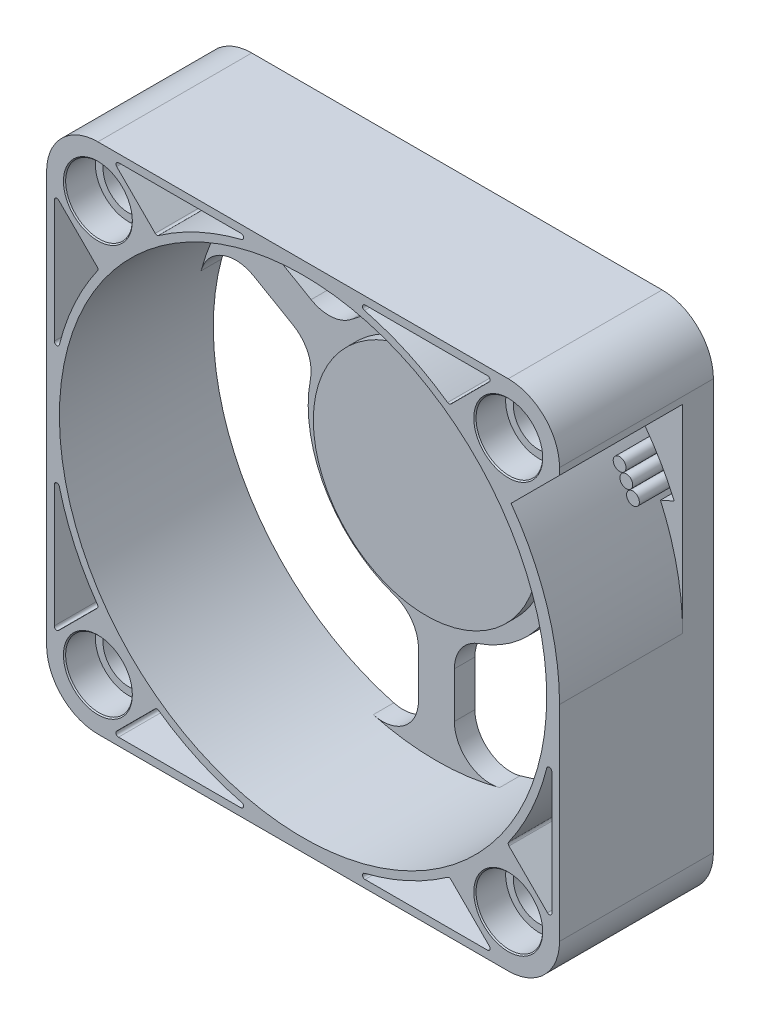
SolidWorks part; units mm, degrees
material "ABS"
ref_plane "Спереди" through (0, 0, 0) normal (0, 0, 1) x (1, 0, 0)
ref_plane "Сверху" through (0, 0, 0) normal (0, 1, 0) x (1, 0, 0)
ref_plane "Справа" through (0, 0, 0) normal (1, 0, 0) x (0, 0, -1)
sketch "Эскиз1" plane through (0, 0, 0) normal (0, 0, 1) x (1, 0, 0)
  line L0 (0, 25) -> (0, -25) construction
  line L1 (-20, -25) -> (20, -25)
  line L2 (-25, -20) -> (-25, 20)
  line L3 (-20, 25) -> (20, 25)
  line L4 (25, -20) -> (25, 20)
  line L5 (1.75, -12.3769) -> (1.75, -23.6854)
  line L6 (-1.75, -12.3769) -> (-1.75, -23.6854)
  line L7 (0, 0) -> (20.5681, 11.875) construction
  line L8 (0, 0) -> (-20.5681, 11.875) construction
  line L9 (-19.6372, 13.3583) -> (-9.8437, 7.704)
  line L10 (-21.3872, 10.3272) -> (-11.5937, 4.6729)
  line L11 (-11.5937, 4.6729) -> (-9.8437, 7.704) construction
  line L12 (-1.75, -12.3769) -> (1.75, -12.3769) construction
  line L13 (8.6423, 9.0311) -> (18.5935, 14.7764)
  line L14 (22.0935, 8.7143) -> (12.1423, 2.9689)
  line L15 (12.1423, 2.9689) -> (8.6423, 9.0311) construction
  arc A0 (-20, -25) -> (-25, -20) centre (-20, -20) cw
  arc A1 (20, -25) -> (25, -20) centre (20, -20) ccw
  arc A2 (20, 25) -> (25, 20) centre (20, 20) cw
  arc A3 (-25, 20) -> (-20, 25) centre (-20, 20) cw
  circle A4 centre (0, 0) radius 12.5
  circle A5 centre (0, 0) radius 23.75
  arc A6 (-16.7861, 16.8014) -> (-16.0624, 11.2943) centre (-14.3124, 14.3254) ccw
  arc A7 (-22.9435, 6.1365) -> (-17.8124, 8.2633) centre (-19.5624, 5.2322) cw
  arc A8 (-12.2142, 9.0726) -> (-8.1752, 9.456) centre (-10.4642, 12.1037) ccw
  arc A9 (-13.9642, 6.0415) -> (-12.2767, 2.3519) centre (-15.7142, 3.0104) cw
  arc A10 (-4.1016, -11.8079) -> (-1.75, -15.1141) centre (-5.25, -15.1141) cw
  arc A11 (1.75, -15.1141) -> (4.1016, -11.8079) centre (5.25, -15.1141) cw
  arc A12 (1.75, -19.5576) -> (6.1574, -22.9379) centre (5.25, -19.5576) ccw
  arc A13 (-1.75, -19.5576) -> (-6.1574, -22.9379) centre (-5.25, -19.5576) cw
  arc A14 (6.9999, 10.3562) -> (10.7099, 10.2248) centre (8.9599, 13.2559) ccw
  arc A15 (12.4687, 0.884) -> (14.2099, 4.1627) centre (15.9599, 1.1316) cw
  arc A16 (18.2059, 6.4697) -> (23.4051, 4.033) centre (19.9559, 3.4386) cw
  arc A17 (14.7059, 12.5319) -> (15.1952, 18.2529) centre (12.9559, 15.563) ccw
  dimension "D1" = 5
  dimension "D3" = 25
  dimension "D4" = 47.5
  dimension "D7" = 3.5
  dimension "D2" = 50
  dimension "D5" = 60
  dimension "D6" = 3.5
  dimension "D8" = 7
extrude "Бобышка-Вытянуть1" add sketch "Эскиз1" along normal blind 15 contours A3 L2 A0 L1 A1 L4 A2 L3 A5 | A6 A5 L9 | A5 A7 L10 | L9 A5 L10 A4 | A17 L13 A5 | A14 A4 L13 | A8 L9 A4 | L10 A9 A4 | A4 | L14 A16 A5 | A4 A15 L14 | L14 A5 L13 A4 | L6 A5 L5 A4 | L5 A11 A4 | A4 A10 L6 | L6 A13 A5 | A12 L5 A5 region at (-23.0355, -23.0355, 0) region at (2.2662, -12.8886, 0) region at (0, -18.0937, 0) region at (0, 0, 0) region at (-2.2662, -12.8886, 0) region at (2.7644, -22.6383, 0) region at (-2.7644, -22.6383, 0) region at (-12.295, 4.4817, 0) region at (12.6849, 2.7888, 0) region at (-15.6696, 9.0469, 0) region at (15.5872, 8.9993, 0) region at (21.5701, 7.1376, 0) region at (-20.9876, 8.9251, 0) region at (-10.0287, 8.4069, 0) region at (8.7576, 9.5911, 0) region at (16.9664, 15.1115, 0) region at (-18.2231, 13.7132, 0)
sketch "Эскиз2" plane through (0, 0, 15) normal (0, 0, 1) x (1, 0, 0)
  circle A0 centre (0, 0) radius 23.75
  arc A1 (15.1952, 18.2529) -> (-16.7861, 16.8014) centre (0, 0) ccw construction
extrude "Вырез-Вытянуть1" cut sketch "Эскиз2" against normal blind 13
sketch "Эскиз3" plane through (0, 0, 15) normal (0, 0, 1) x (1, 0, 0)
  line L0 (0, 20) -> (0, -20) construction
  line L1 (-20, -20) -> (20, -20) construction
  line L2 (-20, -20) -> (-20, 20) construction
  line L3 (-20, 20) -> (20, 20) construction
  line L4 (20, -20) -> (20, 20) construction
  dimension "D1" = 40
hole_wizard "Цековка для  болта с шестигранной головкой M51" positions "Эскиз4" profile "Эскиз5" counterbore size "M5" standard "ISO" end condition up to next
sketch "Эскиз4" plane through (0, 0, 15) normal (0, 0, 1) x (1, 0, 0)
  point P0 (-20, 20)
  point P3 (20, 20)
  point P6 (20, -20)
  point P9 (-20, -20)
sketch "Эскиз5" plane through (-20, 20, 15) normal (1, 0, 0) x (0, -1, 0)
  line L0 (0, 0) -> (0, 15)
  line L1 (0, 15) -> (2.5, 15)
  line L3 (2.5, 15) -> (2.5, 3)
  line L4 (3.25, 3) -> (2.5, 3)
  line L5 (3.25, 3) -> (3.25, 0.11)
  line L6 (3.25, 0.11) -> (3.36, 0)
  line L7 (3.36, 0) -> (0, 0)
  line L8 (-3.25, 0.11) -> (-3.36, 0) construction
  line L11 (0, -6.35) -> (0, 107.95) construction
  dimension "Диаметр сквозного отверстия" = 5
  dimension "Глубина сквозного отверстия" = 15
  dimension "Диаметр цековки" = 6.5
  dimension "Глубина цековки" = 3
  dimension "Диаметр передней зенковки" = 6.72
  dimension "Угол передней зенковки" = 90
sketch "Эскиз6" plane through (0, 0, 15) normal (0, 0, 1) x (1, 0, 0)
  line L0 (0, 0) -> (20, 20) construction
  line L1 (6.0467, 24.25) -> (17.9896, 24.25)
  line L2 (-20, 25) -> (20, 25) construction
  line L3 (14.4125, 20.0694) -> (18.1664, 23.8232)
  line L4 (24.25, -6.0467) -> (24.25, -17.9896)
  line L5 (25, -20) -> (25, 20) construction
  line L6 (20.0694, 14.4125) -> (23.8232, 18.1664)
  line L7 (24.25, 17.9896) -> (24.25, 6.0467)
  line L8 (20.0694, -14.4125) -> (23.8232, -18.1664)
  line L9 (14.4125, -20.0694) -> (18.1664, -23.8232)
  line L10 (17.9896, -24.25) -> (6.0467, -24.25)
  line L11 (-6.0467, -24.25) -> (-17.9896, -24.25)
  line L12 (-14.4125, -20.0694) -> (-18.1664, -23.8232)
  line L13 (-20.0694, -14.4125) -> (-23.8232, -18.1664)
  line L14 (-24.25, -17.9896) -> (-24.25, -6.0467)
  line L15 (-24.25, 6.0467) -> (-24.25, 17.9896)
  line L16 (-20.0694, 14.4125) -> (-23.8232, 18.1664)
  line L17 (-14.4125, 20.0694) -> (-18.1664, 23.8232)
  line L18 (-17.9896, 24.25) -> (-6.0467, 24.25)
  arc A0 (23.7576, 5.9856) -> (20.0416, 14.0919) centre (0, 0) ccw
  arc A1 (6.0467, 24.25) -> (5.9856, 23.7576) centre (6.0467, 24) ccw
  arc A2 (18.1664, 23.8232) -> (17.9896, 24.25) centre (17.9896, 24) ccw
  arc A3 (14.0919, 20.0416) -> (14.4125, 20.0694) centre (14.2357, 20.2461) ccw
  arc A4 (23.8232, 18.1664) -> (24.25, 17.9896) centre (24, 17.9896) cw
  arc A5 (24.25, 6.0467) -> (23.7576, 5.9856) centre (24, 6.0467) cw
  arc A6 (20.0694, 14.4125) -> (20.0416, 14.0919) centre (20.2461, 14.2357) ccw
  arc A7 (14.0919, 20.0416) -> (5.9856, 23.7576) centre (0, 0) ccw
  arc A8 (24.25, -6.0467) -> (23.7576, -5.9856) centre (24, -6.0467) ccw
  arc A9 (23.8232, -18.1664) -> (24.25, -17.9896) centre (24, -17.9896) ccw
  arc A10 (20.0416, -14.0919) -> (20.0694, -14.4125) centre (20.2461, -14.2357) ccw
  arc A11 (20.0416, -14.0919) -> (23.7576, -5.9856) centre (0, 0) ccw
  arc A12 (18.1664, -23.8232) -> (17.9896, -24.25) centre (17.9896, -24) cw
  arc A13 (6.0467, -24.25) -> (5.9856, -23.7576) centre (6.0467, -24) cw
  arc A14 (5.9856, -23.7576) -> (14.0919, -20.0416) centre (0, 0) ccw
  arc A15 (14.4125, -20.0694) -> (14.0919, -20.0416) centre (14.2357, -20.2461) ccw
  arc A16 (-6.0467, -24.25) -> (-5.9856, -23.7576) centre (-6.0467, -24) ccw
  arc A17 (-18.1664, -23.8232) -> (-17.9896, -24.25) centre (-17.9896, -24) ccw
  arc A18 (-14.0919, -20.0416) -> (-14.4125, -20.0694) centre (-14.2357, -20.2461) ccw
  arc A19 (-14.0919, -20.0416) -> (-5.9856, -23.7576) centre (0, 0) ccw
  arc A20 (-23.8232, -18.1664) -> (-24.25, -17.9896) centre (-24, -17.9896) cw
  arc A21 (-24.25, -6.0467) -> (-23.7576, -5.9856) centre (-24, -6.0467) cw
  arc A22 (-23.7576, -5.9856) -> (-20.0416, -14.0919) centre (0, 0) ccw
  arc A23 (-20.0694, -14.4125) -> (-20.0416, -14.0919) centre (-20.2461, -14.2357) ccw
  arc A24 (-24.25, 6.0467) -> (-23.7576, 5.9856) centre (-24, 6.0467) ccw
  arc A25 (-23.8232, 18.1664) -> (-24.25, 17.9896) centre (-24, 17.9896) ccw
  arc A26 (-20.0416, 14.0919) -> (-20.0694, 14.4125) centre (-20.2461, 14.2357) ccw
  arc A27 (-20.0416, 14.0919) -> (-23.7576, 5.9856) centre (0, 0) ccw
  arc A28 (-18.1664, 23.8232) -> (-17.9896, 24.25) centre (-17.9896, 24) cw
  arc A29 (-6.0467, 24.25) -> (-5.9856, 23.7576) centre (-6.0467, 24) cw
  arc A30 (-5.9856, 23.7576) -> (-14.0919, 20.0416) centre (0, 0) ccw
  arc A31 (-14.4125, 20.0694) -> (-14.0919, 20.0416) centre (-14.2357, 20.2461) ccw
  point P86 (0, 0)
  dimension "D1" = 49
  dimension "D4" = 0.25
  dimension "D2" = 0.75
  dimension "D3" = 4
  dimension "D5" = 0.75
  dimension "D6" = 4
  dimension "D7" = 4
extrude "Вырез-Вытянуть2" cut sketch "Эскиз6" against normal blind 13 contours A7 A3 L3 A2 L1 A1 | L17 A31 A30 A29 L18 A28 | A27 A26 L16 A25 L15 A24 | L13 A23 A22 A21 L14 A20 | A19 A18 L12 A17 L11 A16 | L9 A15 A14 A13 L10 A12 | A11 A10 L8 A9 L4 A8 region at (12.8617, 22.8737, 15) region at (22.8737, -12.8617, 15) region at (12.8617, -22.8737, 15) region at (-12.8617, -22.8737, 15) region at (-22.8737, -12.8617, 15) region at (-22.8737, 12.8617, 15) region at (-12.8617, 22.8737, 15)
sketch "Эскиз7" plane through (0, 0, 0) normal (1, 0, 0) x (0, 0, -1)
  line L0 (0, 0) -> (-15, 0) construction
  line L1 (-15, 23.75) -> (-15, -23.75) construction
  line L4 (-3, 0) -> (-3, 11)
  line L5 (-3, 11) -> (-2, 11)
  line L6 (-3, 0) -> (-2, 0)
  line L8 (-2, 16.8014) -> (-2, 6.1365) construction
  line L9 (-2, 11) -> (-2, 0)
  line L10 (-2, 2.3519) -> (-2, -11.8079) construction
  dimension "D1" = 1
  dimension "D5" = 11
revolve "Повернуть1" add sketch "Эскиз7" angle 360 about L0
sketch "Эскиз8" plane through (0, 0, 15) normal (0, 0, 1) x (1, 0, 0)
  line L0 (0, 0) -> (20, 20) construction
  line L1 (20.2784, 14.6215) -> (25, 19.3431)
  line L2 (25, -20) -> (25, 20) construction
  line L3 (25, 19.3431) -> (25, 0)
  arc A0 (25, 0) -> (20.2784, 14.6215) centre (0, 0) ccw
  dimension "D1" = 4
extrude "Вырез-Вытянуть3" cut sketch "Эскиз8" against normal blind 12
sketch "Эскиз9" plane through (0, 0, 3) normal (0, 0, 1) x (1, 0, 0)
  line L0 (20.2784, 14.6215) -> (21.339, 15.6822)
  line L1 (25, 19.3431) -> (20.2784, 14.6215) construction
  line L2 (22.8386, 10.1684) -> (24.1923, 10.7711)
  arc A0 (20.2784, 14.6215) -> (22.8386, 10.1684) centre (0, 0) cw
  arc A1 (25, 0) -> (20.2784, 14.6215) centre (0, 0) ccw construction
  arc A2 (21.339, 15.6822) -> (24.1923, 10.7711) centre (0, 0) cw
  dimension "D1" = 1.5
  dimension "D2" = 21
extrude "Вырез-Вытянуть4" cut sketch "Эскиз9" against normal through all
sketch "Эскиз10" plane through (0, 0, 0) normal (0, 0, -1) x (-1, 0, 0)
  line L0 (0, 0) -> (-22.5167, 13) construction
  line L1 (0, 0) -> (0, 25) construction
  line L2 (20, 25) -> (-20, 25) construction
  line L3 (-21.5167, 14.7321) -> (-9.3923, 7.7321)
  line L4 (-23.5167, 11.2679) -> (-11.3923, 4.2679)
  line L5 (-23.5167, 11.2679) -> (-21.5167, 14.7321)
  line L6 (-11.3923, 4.2679) -> (-9.3923, 7.7321)
  dimension "D1" = 60
  dimension "D2" = 4
  dimension "D3" = 12
  dimension "D4" = 14
extrude "Вырез-Вытянуть5" cut sketch "Эскиз10" against normal blind 1.5
ref_plane "Плоскость1" through (0.65, -1.1258, 0) normal (-0.5, 0.866, 0) x (0.866, 0.5, 0)
sketch "Эскиз11" plane through (0.65, -1.1258, 0) normal (-0.5, 0.866, 0) x (0.866, 0.5, 0)
  line L0 (12, -0.75) -> (24.7, -0.75)
  line L1 (12, -1.5) -> (12, 0) construction
  line L2 (25.7, -1.75) -> (25.7, -5.75)
  arc A0 (24.7, -0.75) -> (25.7, -1.75) centre (24.7, -1.75) cw
  dimension "D2" = 1
  dimension "D1" = 13.7
  dimension "D3" = 5
sketch "Эскиз12" plane through (10.3923, 6, 0) normal (0.866, 0.5, 0) x (0, 0, -1)
  circle A0 centre (-0.75, -1.3) radius 0.625
  dimension "D1" = 1.25
sweep "По траектории1" add profiles "Эскиз12" path "Эскиз11"
pattern_linear "Линейный массив1" count 3 spacing 1.3 along (-0.5, 0.866, 0) of "По траектории1"
